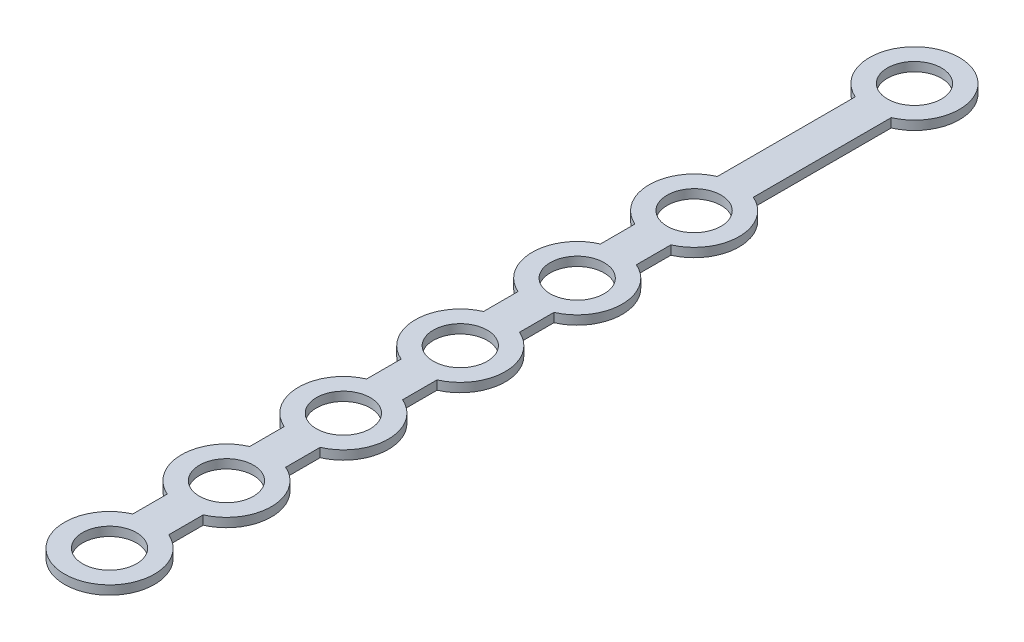
SolidWorks part; units mm, degrees
material "Copper"
ref_plane "Front Plane" through (0, 0, 0) normal (0, 0, 1) x (1, 0, 0)
ref_plane "Top Plane" through (0, 0, 0) normal (0, 1, 0) x (1, 0, 0)
ref_plane "Right Plane" through (0, 0, 0) normal (1, 0, 0) x (0, 0, -1)
sketch "Sketch1" plane through (0, 0, 0) normal (0, 1, 0) x (1, 0, 0)
  circle A0 centre (0, 0) radius 10
  dimension "D1" = 20
base flange "Base-Flange1" sketch "Sketch1" thickness 2 reverse thickness direction no parameters "D1"=1
sketch "Sketch6" plane through (0, 0, 0) normal (0, 1, 0) x (1, 0, 0)
  circle A0 centre (0, 0) radius 6
  dimension "D1" = 12
extrude "Cut-Extrude1" cut sketch "Sketch6" against normal through all normal cut yes
sketch "Sketch8" plane through (0, 0, 0) normal (0, 1, 0) x (1, 0, 0)
  circle A0 centre (0, 26) radius 10
  dimension "D1" = 20
  dimension "D2" = 26
base flange "Base-Flange2" sketch "Sketch8" thickness 2 reverse thickness direction no parameters "D1"=1
sketch "Sketch11" plane through (0, 0, 0) normal (0, 1, 0) x (1, 0, 0)
  circle A0 centre (0, 26) radius 6
  dimension "D1" = 12
extrude "Cut-Extrude2" cut sketch "Sketch11" against normal through all
sketch "Sketch12" plane through (0, 0, 0) normal (0, 1, 0) x (1, 0, 0)
  line L1 (13, 13) -> (-13, 13)
  line L2 (13, 13) -> (13, -13)
  line L3 (13, -13) -> (-13, -13)
  line L4 (-13, 13) -> (-13, -13)
  point P4 (13, 0)
  dimension "D1" = 26
  dimension "D2" = 26
  dimension "D3" = 13
  dimension "D4" = 13
sketch "Sketch13" plane through (0, 0, 0) normal (0, 1, 0) x (1, 0, 0)
  line L0 (13, 13) -> (-13, 13) construction
  line L1 (-4, 13) -> (4, 13)
  line L2 (-4, 13) -> (-4, 9.1652)
  line L3 (-4, 9.1652) -> (4, 9.1652)
  line L4 (4, 13) -> (4, 9.1652)
  line L5 (13, 13) -> (13, -13) construction
  circle A0 centre (0, 0) radius 10 construction
  point P8 (0, 9.1652)
  dimension "D1" = 8
  dimension "D2" = 13
base flange "Tab1" sketch "Sketch13" thickness 2 reverse thickness direction no parameters "D1"=1
sketch "Sketch16" plane through (0, 0, 0) normal (0, 1, 0) x (1, 0, 0)
  line L1 (4, 13) -> (-4, 13)
  line L2 (4, 13) -> (4, 16.8348)
  line L3 (4, 16.8348) -> (-4, 16.8348)
  line L4 (-4, 13) -> (-4, 16.8348)
  circle A0 centre (0, 26) radius 10 construction
  dimension "D1" = 8
base flange "Tab2" sketch "Sketch16" thickness 2 reverse thickness direction no parameters "D1"=1
sketch "Sketch19" plane through (0, 0, 0) normal (0, 1, 0) x (1, 0, 0)
  line L1 (13, 13) -> (-13, 13)
  line L2 (13, 13) -> (13, 39)
  line L3 (13, 39) -> (-13, 39)
  line L4 (-13, 13) -> (-13, 39)
  line L5 (-13, 39) -> (13, 39)
  line L6 (-13, 39) -> (-13, 65)
  line L7 (-13, 65) -> (13, 65)
  line L8 (13, 39) -> (13, 65)
  line L9 (-13, 65) -> (13, 65)
  line L10 (-13, 65) -> (-13, 91)
  line L11 (-13, 91) -> (13, 91)
  line L12 (13, 65) -> (13, 91)
  line L13 (-13, 91) -> (13, 91)
  line L14 (-13, 91) -> (-13, 117)
  line L15 (-13, 117) -> (13, 117)
  line L16 (13, 91) -> (13, 117)
  line L17 (-13, 117) -> (13, 117)
  line L18 (-13, 117) -> (-13, 143)
  line L19 (-13, 143) -> (13, 143)
  line L20 (13, 117) -> (13, 143)
  line L21 (-13, 143) -> (13, 143)
  line L22 (-13, 143) -> (-13, 169)
  line L23 (-13, 169) -> (13, 169)
  line L24 (13, 143) -> (13, 169)
  line L25 (-13, 169) -> (13, 169)
  line L26 (-13, 169) -> (-13, 189)
  line L27 (-13, 189) -> (13, 189)
  line L28 (13, 169) -> (13, 189)
  dimension "D1" = 26
  dimension "D2" = 26
  dimension "D3" = 26
  dimension "D4" = 26
  dimension "D5" = 26
  dimension "D6" = 26
  dimension "D7" = 26
  dimension "D8" = 20
sketch "Sketch23" plane through (0, 0, 0) normal (0, 1, 0) x (1, 0, 0)
  line L0 (13, 13) -> (13, 39) construction
  line L1 (4, 35.1652) -> (-4, 35.1652)
  line L2 (4, 35.1652) -> (4, 42.9432)
  line L3 (4, 42.9432) -> (-4, 42.9432)
  line L4 (-4, 35.1652) -> (-4, 42.9432)
  line L5 (4, 68.9432) -> (-4, 68.9432)
  line L6 (4, 94.9432) -> (-4, 94.9432)
  line L7 (4, 120.9432) -> (-4, 120.9432)
  line L8 (4, 61.1652) -> (4, 68.9432)
  line L9 (-4, 61.1652) -> (-4, 68.9432)
  line L10 (4, 61.1652) -> (-4, 61.1652)
  line L11 (4, 87.1652) -> (4, 94.9432)
  line L12 (-4, 87.1652) -> (-4, 94.9432)
  line L13 (4, 87.1652) -> (-4, 87.1652)
  line L14 (4, 113.1652) -> (4, 120.9432)
  line L15 (-4, 113.1652) -> (-4, 120.9432)
  line L16 (4, 113.1652) -> (-4, 113.1652)
  line L17 (4, 139.1652) -> (4, 146.9432)
  line L18 (-4, 139.1652) -> (-4, 146.9432)
  line L19 (4, 139.1652) -> (-4, 139.1652)
  line L20 (4, 160.1652) -> (4, 146.9432)
  line L22 (4, 160.1652) -> (4, 169.0439)
  line L23 (-4, 160.1652) -> (-4, 146.9432)
  line L25 (-4, 169.0439) -> (-4, 160.1652)
  line L26 (-4, 169.0439) -> (-4, 173.0414)
  line L27 (-4, 173.0414) -> (4, 173.0414)
  line L28 (4, 173.0414) -> (4, 169.0439)
  arc A0 (4, 16.8348) -> (-4, 16.8348) centre (0, 26) ccw construction
  dimension "D1" = 8
  dimension "D3" = 4
  dimension "D4" = 5
sketch "Sketch20" plane through (0, 0, 0) normal (0, 1, 0) x (1, 0, 0)
  line L0 (3.8653, 94.9774) -> (3.8653, 87.2228)
  line L2 (-4.1342, 68.8946) -> (-4.1342, 61.1054)
  line L4 (3.8653, 68.9774) -> (3.8653, 61.2228)
  line L5 (-4.1342, 94.8946) -> (-4.1342, 87.1054)
  line L6 (3.8653, 120.9774) -> (3.8653, 113.2228)
  line L7 (-4.1342, 120.8946) -> (-4.1342, 113.1054)
  line L8 (3.8653, 146.9774) -> (3.8653, 139.2228)
  line L9 (-4.1342, 146.8946) -> (-4.1342, 139.1054)
  line L10 (-4.1342, 61.1054) -> (3.8653, 61.2228)
  line L11 (-4.1342, 146.8946) -> (-4.1342, 159.8946)
  line L12 (-4.1342, 159.8946) -> (3.8653, 159.7772)
  line L13 (3.8653, 159.7772) -> (3.8653, 146.9774)
  line L14 (-4.1342, 87.1054) -> (3.8653, 87.2228)
  line L15 (-4.1342, 113.1054) -> (3.8653, 113.2228)
  line L16 (-4.1342, 139.1054) -> (3.8653, 139.2228)
  line L18 (-4.1342, 68.8946) -> (3.8653, 68.9774)
  line L20 (-4.1342, 94.8946) -> (3.8653, 94.9774)
  line L21 (-4.1342, 120.8946) -> (3.8653, 120.9774)
  line L23 (-4.1342, 146.8946) -> (3.8653, 146.9774) [skipped]
  circle A0 centre (0, 52) radius 10
  circle A1 centre (0, 78) radius 10
  circle A2 centre (0, 104) radius 10
  circle A3 centre (0, 130) radius 10
  circle A4 centre (0, 169) radius 10
  point P15 (3.8653, 65.1001)
  dimension "D1" = 20
  dimension "D3" = 20
  dimension "D4" = 20
  dimension "D5" = 20
  dimension "D6" = 20
  dimension "D2" = 52
  dimension "D7" = 26
  dimension "D8" = 26
  dimension "D9" = 26
  dimension "D10" = 39
  dimension "D11" = 8
  dimension "D12" = 13.1001
  dimension "D13" = 4
  dimension "D14" = 4
  dimension "D15" = 4
sketch "Sketch30" plane through (0, 0, 0) normal (0, 1, 0) x (1, 0, 0)
  line L0 (13, 39) -> (-13, 39) construction
  line L1 (3.9999, 35.1652) -> (-4.0001, 35.1652)
  line L2 (3.9999, 35.1652) -> (3.9999, 39)
  line L3 (3.9999, 39) -> (-4.0001, 39)
  line L4 (-4.0001, 35.1652) -> (-4.0001, 39)
  line L5 (13, 13) -> (13, 39) construction
  arc A0 (4, 16.8348) -> (-4, 16.8348) centre (0, 26) ccw construction
  point P9 (-0.0001, 35.1652)
  dimension "D1" = 13.0001
  dimension "D2" = 8
sketch "Sketch33" plane through (0, 0, 0) normal (0, 1, 0) x (1, 0, 0)
  line L1 (-13, 169) -> (13, 169) construction
  circle A0 centre (0, 52) radius 10
  circle A1 centre (0, 26) radius 6 construction
  circle A2 centre (0, 78) radius 10
  circle A3 centre (0, 104) radius 10
  circle A4 centre (0, 130) radius 10
  circle A5 centre (0, 179) radius 10
  dimension "D1" = 20
  dimension "D5" = 20
  dimension "D2" = 26
  dimension "D4" = 10
  dimension "D3" = 4
extrude "Boss-Extrude2" add sketch "Sketch33" against normal blind 2 separate body
extrude "Boss-Extrude3" add sketch "Sketch23" against normal blind 2
sketch "Sketch41" plane through (0, 0, 0) normal (0, 1, 0) x (1, 0, 0)
  line L0 (-13, 169) -> (-13, 189) construction
  line L1 (-13, 189) -> (13, 189) construction
  circle A0 centre (0, 52) radius 6
  circle A1 centre (0, 78) radius 6
  circle A2 centre (0, 104) radius 6
  circle A3 centre (0, 130) radius 6
  circle A4 centre (0, 179) radius 6
  dimension "D1" = 12
  dimension "D2" = 12
  dimension "D3" = 12
  dimension "D4" = 26
  dimension "D5" = 12
  dimension "D6" = 12
  dimension "D8" = 10
  dimension "D7" = 13
extrude "Cut-Extrude3" cut sketch "Sketch41" against normal blind 2 normal cut yes
sketch "Bend-Lines1" [suppressed] plane through (0, 0, 0) normal (0, 1, 0) x (1, 0, 0)
sketch "Bounding-Box1" [suppressed] plane through (0, 0, 0) normal (0, 1, 0) x (1, 0, 0)
sheet metal parameters "Sheet-Metal1" thickness 2 parameters "D1"=1
flat pattern "Flat-Pattern1" [suppressed]
sketch "Bend-Lines2" plane through (0, 0, 0) normal (0, 1, 0) x (1, 0, 0)
sketch3d "Bounding-Box2" [suppressed]
  line L0 (-10.0341, -9.9657, 0) -> (9.9656, -10.0341, 0) construction
  line L1 (-9.9656, 10.034, 0) -> (10.0341, 9.9656, 0) construction
  line L2 (-10.0341, -9.9657, 0) -> (-9.9656, 10.034, 0) construction
  line L3 (9.9656, -10.0341, 0) -> (10.0341, 9.9656, 0) construction
sheet metal parameters "Sheet-Metal2" thickness 2 parameters "D1"=1
flat pattern "Flat-Pattern1"
sketch "Bend-Lines2" plane through (0, 0, 0) normal (0, 1, 0) x (1, 0, 0)
sketch3d "Bounding-Box2" [suppressed]
  line L0 (10.0341, -9.9657, 0) -> (-9.9656, -10.0341, 0) construction
  line L1 (9.9656, 10.034, 0) -> (-10.0341, 9.9656, 0) construction
  line L2 (10.0341, -9.9657, 0) -> (9.9656, 10.034, 0) construction
  line L3 (-9.9656, -10.0341, 0) -> (-10.0341, 9.9656, 0) construction
sheet metal parameters "Sheet-Metal3" thickness 2 parameters "D1"=1
flat pattern "Flat-Pattern3"
sketch "Bend-Lines3" plane through (0, 0, 0) normal (0, 1, 0) x (1, 0, 0)
sketch3d "Bounding-Box3" [suppressed]
  line L0 (-10.0341, -9.9657, 0) -> (9.9656, -10.0341, 0) construction
  line L1 (-9.9656, 10.034, 0) -> (10.0341, 9.9656, 0) construction
  line L2 (-10.0341, -9.9657, 0) -> (-9.9656, 10.034, 0) construction
  line L3 (9.9656, -10.0341, 0) -> (10.0341, 9.9656, 0) construction
sheet metal parameters "Sheet-Metal4" thickness 2 parameters "D1"=1
flat pattern "Flat-Pattern3"
sketch "Bend-Lines3" plane through (0, 0, 0) normal (0, 1, 0) x (1, 0, 0)
sketch3d "Bounding-Box3" [suppressed]
  line L0 (10.0341, -9.9657, 0) -> (-9.9656, -10.0341, 0) construction
  line L1 (9.9656, 10.034, 0) -> (-10.0341, 9.9656, 0) construction
  line L2 (10.0341, -9.9657, 0) -> (9.9656, 10.034, 0) construction
  line L3 (-9.9656, -10.0341, 0) -> (-10.0341, 9.9656, 0) construction
sheet metal parameters "Sheet-Metal5" thickness 2 parameters "D1"=1
flat pattern "Flat-Pattern5"
sketch "Bend-Lines4" plane through (0, 0, 0) normal (0, 1, 0) x (1, 0, 0)
sketch3d "Bounding-Box4" [suppressed]
  line L0 (-10, 13, 0) -> (-10, -10, 0) construction
  line L1 (10, 13, 0) -> (10, -10, 0) construction
  line L2 (-10, 13, 0) -> (10, 13, 0) construction
  line L3 (-10, -10, 0) -> (10, -10, 0) construction
sheet metal parameters "Sheet-Metal6" thickness 2 parameters "D1"=1
flat pattern "Flat-Pattern6"
sketch "Bend-Lines5" plane through (0, 0, 0) normal (0, 1, 0) x (1, 0, 0)
sketch3d "Bounding-Box5" [suppressed]
  line L0 (10, 36, 0) -> (10, -10, 0) construction
  line L1 (-10, 36, 0) -> (-10, -10, 0) construction
  line L2 (10, 36, 0) -> (-10, 36, 0) construction
  line L3 (10, -10, 0) -> (-10, -10, 0) construction
sheet metal parameters "Sheet-Metal24" thickness 2 parameters "D1"=1
flat pattern "Flat-Pattern24"
sketch "Bend-Lines12" plane through (0, 0, 0) normal (0, 1, 0) x (1, 0, 0)
sketch3d "Bounding-Box12" [suppressed]
  line L0 (10, 179, 0) -> (10, -10, 0) construction
  line L1 (-10, 179, 0) -> (-10, -10, 0) construction
  line L2 (10, 179, 0) -> (-10, 179, 0) construction
  line L3 (10, -10, 0) -> (-10, -10, 0) construction
sheet metal parameters "Sheet-Metal26" thickness 2 parameters "D1"=1
flat pattern "Flat-Pattern24"
sketch "Bend-Lines12" plane through (0, 0, 0) normal (0, 1, 0) x (1, 0, 0)
sketch3d "Bounding-Box12" [suppressed]
  line L0 (10, 189, 0) -> (10, -10, 0) construction
  line L1 (-10, 189, 0) -> (-10, -10, 0) construction
  line L2 (10, 189, 0) -> (-10, 189, 0) construction
  line L3 (10, -10, 0) -> (-10, -10, 0) construction
sheet metal parameters "Sheet-Metal27" thickness 2 parameters "D1"=1
flat pattern "Flat-Pattern27"
sketch "Bend-Lines14" plane through (0, 0, 0) normal (0, 1, 0) x (1, 0, 0)
sketch3d "Bounding-Box14" [suppressed]
  line L0 (10, 170.7664, 0) -> (-10, 170.7664, 0) construction
  line L1 (10, 189, 0) -> (-10, 189, 0) construction
  line L2 (10, 170.7664, 0) -> (10, 189, 0) construction
  line L3 (-10, 170.7664, 0) -> (-10, 189, 0) construction
